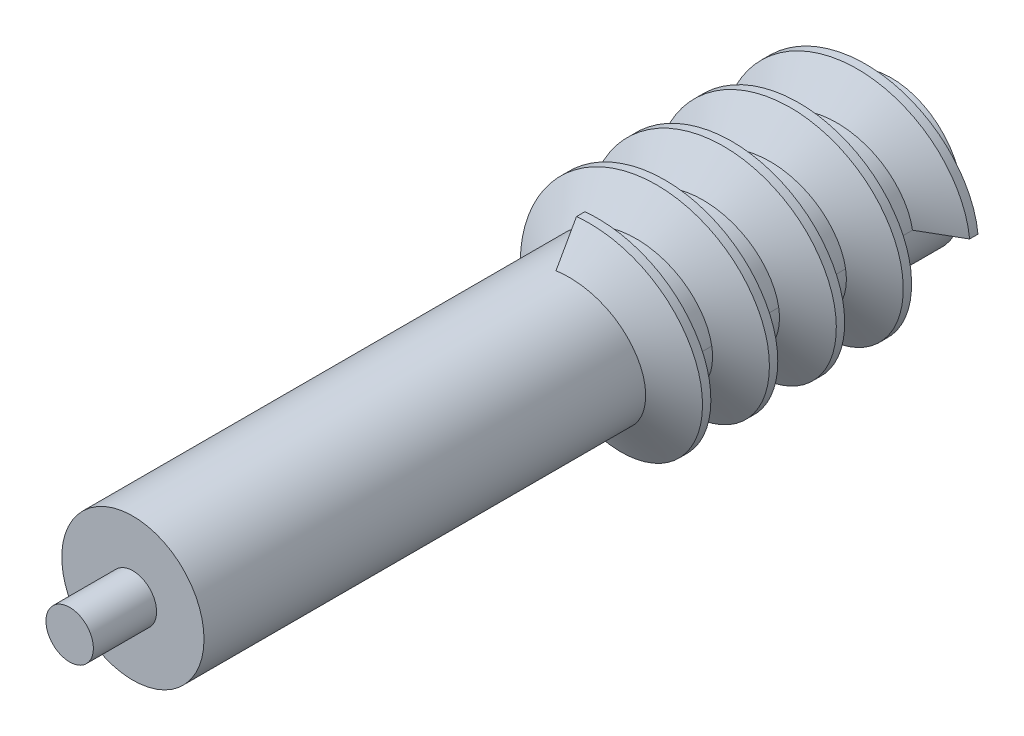
SolidWorks part; units mm, degrees
ref_plane "Front Plane" through (0, 0, 0) normal (0, 0, 1) x (1, 0, 0)
ref_plane "Top Plane" through (0, 0, 0) normal (0, 1, 0) x (1, 0, 0)
ref_plane "Right Plane" through (0, 0, 0) normal (1, 0, 0) x (0, 0, -1)
sketch "Sketch1" plane through (0, 0, 0) normal (0, 0, 1) x (1, 0, 0)
  circle A0 centre (0, 0) radius 2.25
  dimension "D1" = 4.5
extrude "Boss-Extrude1" add sketch "Sketch1" along normal blind 24
thread "Thread1" pitch 2.1167 method extrude profile "Thread Profile1" start angle 0, offset 0, length 9, pitch 2.1167, diameter 4.5
ref_plane "Plane1" through (2.25, 0, 0) normal (0, -1, 0) x (1, 0, 0)
sketch "Thread Profile1" plane through (2.25, 0, 0) normal (0, -1, 0) x (1, 0, 0)
  line L0 (0, 0) -> (0, 2.1167) construction
  line L1 (0, 0) -> (1.1457, 0.6615)
  line L2 (1.1457, 0.6615) -> (1.1457, 0.926)
  line L3 (1.1457, 0.926) -> (0, 1.5875)
  line L4 (1.1457, 0.7937) -> (0, 0.7937) construction
  line L11 (0, 0) -> (0, 1.5875)
  point P2 (0, 0)
  dimension "Pitch" = 2.1167
  dimension "Profile_Angle" = 60
  dimension "Profile_Land" = 0.2646
  dimension "Profile_Height" = 1.1457
sketch "Sketch4" plane through (0, 0, 24) normal (0, 0, 1) x (1, 0, 0)
  circle A0 centre (0, 0) radius 0.75
  dimension "D1" = 1.5
extrude "Boss-Extrude2" add sketch "Sketch4" along normal blind 2
